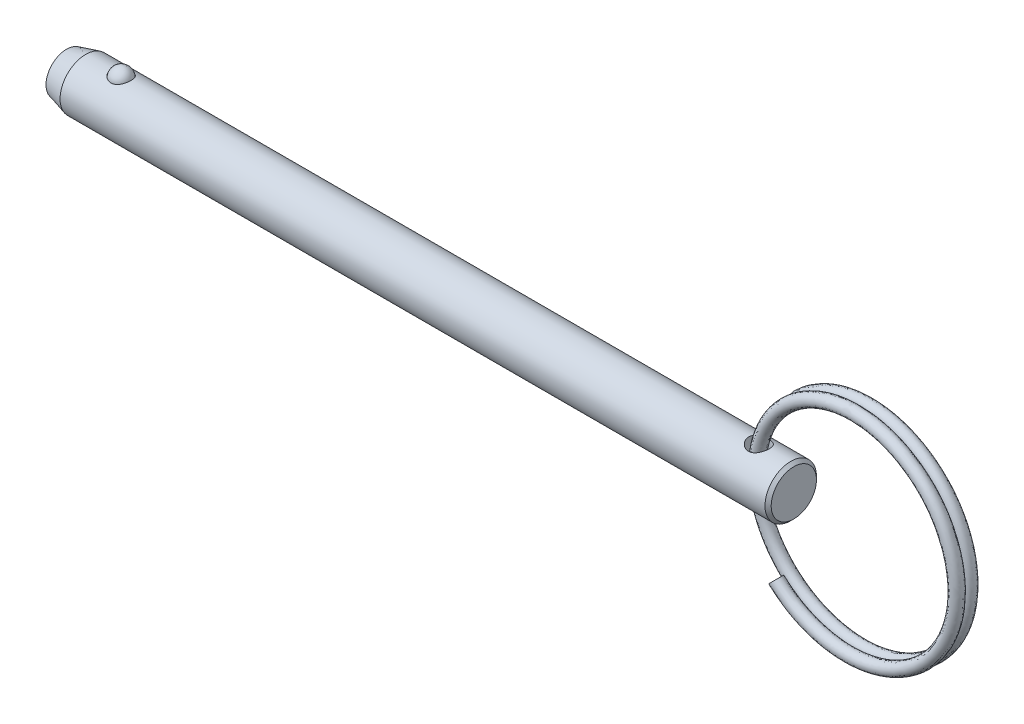
SolidWorks part; units mm, degrees
material "AISI 304"
ref_plane "Front" through (0, 0, 0) normal (0, 0, 1) x (1, 0, 0)
ref_plane "Top" through (0, 0, 0) normal (0, 1, 0) x (1, 0, 0)
ref_plane "Right" through (0, 0, 0) normal (1, 0, 0) x (0, 0, -1)
sketch "Sketch1" plane through (0, 0, 0) normal (0, 0, 1) x (1, 0, 0)
  line L0 (5.588, 2.794) -> (5.207, 3.175)
  line L1 (5.207, 3.175) -> (5.588, 3.175) construction
  line L4 (5.588, 2.794) -> (5.588, 0)
  line L5 (5.588, 3.175) -> (5.588, 2.794) construction
  line L16 (5.207, 3.175) -> (-81.7549, 3.175)
  line L17 (-84.1248, 3.175) -> (-84.1248, 2.54) construction
  line L19 (-81.7549, 3.175) -> (-84.1248, 3.175) construction
  line L22 (-84.1248, -3.175) -> (-81.7549, -3.175) construction
  line L23 (-77.3903, 2.8575) -> (-77.3903, -2.8575) construction
  line L24 (-84.1248, 0) -> (5.588, 0)
  line L27 (5.588, 0) -> (8.382, 0) construction
  line L29 (-84.1248, 0) -> (-84.1248, -2.54) construction
  line L36 (0, 0) -> (0, 3.175) construction
  line L37 (-84.1248, 2.54) -> (-84.1248, 0)
  line L38 (-81.7549, -3.175) -> (5.588, -3.175) construction
  line L39 (-84.1248, -2.54) -> (-84.1248, -3.175) construction
  line L40 (-81.7549, 3.175) -> (-84.1248, 2.54)
  line L42 (-81.7549, -3.175) -> (-84.1248, -2.54) construction
  line L43 (-81.7549, 3.175) -> (-81.7549, -3.175) construction
  circle A2 centre (-77.3903, 2.8575) radius 1.2319 construction
  point P35 (-76.2, 3.175)
  dimension "D2" = 5.715
  dimension "D11" = 0.9144
  dimension "A" = 6.35
  dimension "D" = 5.588
  dimension "E" = 7.2644
  dimension "D3" = 0.381
  dimension "Useable Length" = 76.2
  dimension "D12" = 5.08
  dimension "C" = 7.9248
  dimension "A1" = 15
revolve "Revolve1" add sketch "Sketch1" angle 360 about L27
sketch "Sketch2" plane through (0, 0, 0) normal (0, 0, 1) x (1, 0, 0)
  line L0 (-76.133, 2.8575) -> (-78.6476, 2.8575)
  line L1 (-77.3903, 4.0894) -> (-77.3903, 4.1148) construction
  line L2 (-76.133, 2.8575) -> (-73.6184, 2.8575) construction
  circle A0 centre (-77.3903, 2.8575) radius 1.2319 construction
  circle A1 centre (-77.3903, 2.8575) radius 1.2319 construction
  arc A2 (-78.6476, 2.8575) -> (-76.133, 2.8575) centre (-77.3903, 2.8575) cw
  dimension "D1" = 0.0254
revolve "Cut-Revolve1" cut sketch "Sketch2" angle 360 about L2
sketch "Sketch3" plane through (0, 0, 0) normal (0, 0, 1) x (1, 0, 0)
  line L0 (-76.1584, 2.8575) -> (-78.6222, 2.8575)
  line L1 (-76.1584, 2.8575) -> (-73.6946, 2.8575) construction
  circle A0 centre (-77.3903, 2.8575) radius 1.2319 construction
  arc A1 (-76.1584, 2.8575) -> (-78.6222, 2.8575) centre (-77.3903, 2.8575) ccw
revolve "Revolve2" add sketch "Sketch3" angle 360 about L1
sketch "Sketch4" plane through (0, 0, 0) normal (0, 0, 1) x (1, 0, 0)
  line L1 (1.27, -3.175) -> (2.54, -3.175)
  line L2 (1.27, -3.175) -> (1.27, 3.175)
  line L3 (1.27, 3.175) -> (2.54, 3.175)
  line L4 (2.54, -3.175) -> (2.54, 3.175)
  line L5 (1.27, -3.175) -> (1.27, -4.445) construction
  line L6 (2.54, 3.175) -> (5.588, 3.175) construction
  line L8 (0, -3.175) -> (0, 3.175) construction
  line L9 (0, 0) -> (1.27, 0) construction
  line L11 (1.27, 0) -> (2.54, 0) construction
  line L12 (5.207, 3.175) -> (-81.7549, 3.175) construction
  line L14 (-81.7549, -3.175) -> (5.588, -3.175) construction
  dimension "D1" = 2.54
revolve "Cut-Revolve2" cut sketch "Sketch4" angle 360 about L2
sketch "Sketch5" plane through (0, 0, 0) normal (0, 0, 1) x (1, 0, 0)
  line L0 (0, 0) -> (0.293, 0) construction
  line L1 (0.293, 0) -> (0.293, 3.175) construction
  line L2 (5.207, 3.175) -> (-81.7549, 3.175) construction
  line L3 (13.755, 0) -> (27.217, 0) construction
  line L4 (2.54, 3.175) -> (2.247, 3.175) construction
  line L5 (1.27, 3.175) -> (2.54, 3.175) construction
  line L6 (0.6728, 3.175) -> (0.6728, -3.175) construction
  line L7 (0.293, 3.175) -> (0, 3.175) construction
  line L8 (1.27, -3.175) -> (2.54, -3.175) construction
  line L9 (0.6728, -3.175) -> (2.54, -3.175) construction
  line L10 (0.293, 0) -> (13.755, 0) construction
  line L11 (13.755, 0) -> (8.7098, -10.8195) construction
  line L12 (2.247, 3.175) -> (0.6728, 3.175) construction
  line L13 (13.755, 11.938) -> (13.755, 13.462) construction
  line L14 (8.7098, -10.8195) -> (8.3878, -11.5101) construction
  circle A0 centre (13.755, 0) radius 13.462
  circle A1 centre (13.755, 0) radius 11.938 construction
  circle A2 centre (13.755, 0) radius 12.7 construction
  point P26 (13.755, 12.7)
  dimension "D1" = 65
  dimension "R Ring Dia" = 25.4
  dimension "Ring OD" = 1.524
curve "Helix/Spiral1" pitch 1.5494 height 1.3557 radius 13.462 left hand yes centre (13.755, 0, 0) axis (0, 0, -1) start towards (1, 0, 0)
sketch "Sketch6" plane through (114.0038, 0, 0) normal (0, 1, 0) x (0, 0, -1)
  line L0 (0, 112.1868) -> (0, 112.9488) construction
  line L1 (0, 112.9488) -> (0, 113.7108) construction
  circle A0 centre (0, 112.9488) radius 0.762
  dimension "D1" = 1.524
sketch "Sketch7" plane through (0, 0, 0) normal (0, 0, 1) x (1, 0, 0)
  circle A0 centre (13.755, 0) radius 13.462 construction
  circle A1 centre (13.755, 0) radius 13.462
curve "Helix/Spiral2" pitch 1.5494 height 1.3557 radius 13.462 left hand yes centre (13.755, 0, 0) axis (0, 0, 1) start towards (1, 0, 0)
sweep "Sweep1" add profiles "Sketch6" path "Helix/Spiral1"
sweep "Sweep2" add profiles "Sketch6<2>" path "Helix/Spiral2"
sketch "Sketch6<2>" plane through (114.0038, 0, 0) normal (0, 1, 0) x (0, 0, -1) same geometry as "Sketch6"
ref_plane "Plane1" through (0, -10.8195, 0) normal (0, 1, 0) x (-1, 0, 0)
sketch "Sketch8" plane through (0, -10.8195, 0) normal (0, 1, 0) x (-1, 0, 0)
  line L0 (296.0902, 0) -> (-8.7098, 0) construction
  line L1 (10.3402, -0.7779) -> (4.5066, -0.7779)
  line L2 (3.5004, -0.9415) -> (-7.2005, -4.517)
  line L3 (-7.2005, 4.517) -> (3.5004, 0.9415)
  line L4 (4.5066, 0.7779) -> (282.8738, 0.7779)
  line L5 (283.88, 0.9415) -> (294.5809, 4.517)
  line L6 (277.0402, -0.7779) -> (282.8738, -0.7779)
  line L7 (283.88, -0.9415) -> (294.5809, -4.517)
  line L8 (10.3402, -0.7779) -> (10.3402, 0.7779) construction
  arc A0 (-7.2005, 4.517) -> (-7.2005, -4.517) centre (-8.7098, 0) ccw
  arc A1 (294.5809, -4.517) -> (294.5809, 4.517) centre (296.0902, 0) ccw
  arc A2 (4.5066, -0.7779) -> (3.5004, -0.9415) centre (4.5066, -3.9529) ccw
  arc A3 (3.5004, 0.9415) -> (4.5066, 0.7779) centre (4.5066, 3.9529) ccw
  arc A4 (282.8738, -0.7779) -> (283.88, -0.9415) centre (282.8738, -3.9529) cw
  arc A5 (282.8738, 0.7779) -> (283.88, 0.9415) centre (282.8738, 3.9529) ccw
  point P6 (10.3402, 0)
  point P16 (3.9902, -0.7779)
  point P20 (3.9902, 0.7779)
  point P23 (283.3902, -0.7779)
  point P26 (283.3902, 0.7779)
  dimension "D2" = 4.7625
  dimension "D3" = 1.5557
  dimension "D6" = 3.175
  dimension "Lanyard Length" = 304.8
  dimension "D4" = 6.35
  dimension "D5" = 12.7
ref_plane "Plane2" through (-10.3402, 0, 0) normal (1, 0, 0) x (0, 0, -1)
sketch "Sketch9" plane through (-10.3402, 0, 0) normal (1, 0, 0) x (0, 0, -1)
  circle A0 centre (0.7779, -10.8195) radius 0.7779
sweep "Sweep3" [suppressed] add profiles "Sketch9" path "Sketch8"
sketch "Sketch10" [suppressed] plane through (-10.3402, 0, 0) normal (1, 0, 0) x (0, 0, -1)
  arc A0 (-0.3849, -10.1482) -> (-0.3849, -11.4908) centre (-0.7779, -10.8195) ccw
  circle A1 centre (0.7779, -10.8195) radius 0.7779
  arc A2 (0.3849, -11.4908) -> (0.3849, -10.1482) centre (0.7779, -10.8195) ccw
  arc A3 (-0.3849, -11.4908) -> (0.3849, -11.4908) centre (0, -12.1485) cw
  arc A4 (-0.3869, -9.3301) -> (-0.3869, -12.3089) centre (-0.7779, -10.8195) ccw
  arc A5 (0.3869, -12.3089) -> (0.3869, -9.3301) centre (0.7779, -10.8195) ccw
  circle A6 centre (-0.7779, -10.8195) radius 1.5399 construction
  circle A7 centre (-0.7779, -10.8195) radius 0.7779 construction
  arc A8 (-0.3849, -10.1482) -> (0.3849, -10.1482) centre (0, -9.4905) ccw
  arc A9 (-0.3869, -9.3301) -> (0.3869, -9.3301) centre (0, -7.856) ccw
  arc A10 (0.3869, -12.3089) -> (-0.3869, -12.3089) centre (0, -13.783) ccw
  point P4 (-0.034, -10.2746)
  point P8 (2.3178, -10.502)
  point P9 (0.762, -10.502)
  dimension "D3" = 1.524
  dimension "D4" = 0.762
  dimension "D2" = 0.762
  dimension "D1" = 0
extrude "Extrude1" [suppressed] add sketch "Sketch10" along normal blind 5.715 separate body
sketch "Sketch11" [suppressed] plane through (-277.0402, 0, 0) normal (1, 0, 0) x (0, 0, -1)
  arc A4 (-0.3849, -10.1482) -> (-0.3849, -11.4908) centre (-0.7779, -10.8195) ccw
  arc A5 (0.3849, -11.4908) -> (-0.3849, -11.4908) centre (0, -12.1485) ccw
  arc A6 (0.3849, -11.4908) -> (0.3849, -10.1482) centre (0.7779, -10.8195) ccw
  arc A7 (-0.3849, -10.1482) -> (0.3849, -10.1482) centre (0, -9.4905) ccw
  arc A8 (-0.3849, -10.1482) -> (-0.3849, -11.4908) centre (-0.7779, -10.8195) ccw
  arc A9 (0.3849, -11.4908) -> (-0.3849, -11.4908) centre (0, -12.1485) ccw
  arc A10 (0.3849, -11.4908) -> (0.3849, -10.1482) centre (0.7779, -10.8195) ccw
  arc A11 (-0.3849, -10.1482) -> (0.3849, -10.1482) centre (0, -9.4905) ccw
  arc A12 (-0.3869, -9.3301) -> (-0.3869, -12.3089) centre (-0.7779, -10.8195) ccw
  arc A13 (0.3869, -12.3089) -> (-0.3869, -12.3089) centre (0, -13.783) ccw
  arc A14 (0.3869, -12.3089) -> (0.3869, -9.3301) centre (0.7779, -10.8195) ccw
  arc A15 (-0.3869, -9.3301) -> (0.3869, -9.3301) centre (0, -7.856) ccw
  arc A16 (-0.3869, -9.3301) -> (-0.3869, -12.3089) centre (-0.7779, -10.8195) ccw
  arc A17 (0.3869, -12.3089) -> (-0.3869, -12.3089) centre (0, -13.783) ccw
  arc A18 (0.3869, -12.3089) -> (0.3869, -9.3301) centre (0.7779, -10.8195) ccw
  arc A19 (-0.3869, -9.3301) -> (0.3869, -9.3301) centre (0, -7.856) ccw
  dimension "D1" = 0
  dimension "D2" = 0
extrude "Extrude2" [suppressed] add sketch "Sketch11" against normal blind 5.715 separate body
sketch "Sketch12" plane through (0, -10.8195, 0) normal (0, 1, 0) x (-1, 0, 0)
  line L0 (326.8712, -5.2864) -> (321.3086, -5.2864) construction
  line L1 (326.8712, -5.9214) -> (310.5026, -5.9214)
  line L2 (326.8712, -5.9214) -> (326.8712, -4.6514)
  line L3 (326.8712, -4.6514) -> (310.7265, -4.6514)
  line L4 (310.5026, -5.9214) -> (310.7265, -4.6514) construction
  line L5 (310.5026, -5.9214) -> (295.1212, -0.3231)
  line L6 (321.3086, -5.2864) -> (310.6146, -5.2864) construction
  line L7 (310.7265, -4.6514) -> (295.5555, 0.8704)
  line L8 (295.1212, -0.3231) -> (295.5555, 0.8704)
  line L9 (310.6146, -5.2864) -> (300.5655, -1.6289) construction
  line L10 (300.5655, -1.6289) -> (295.3383, 0.2737) construction
  arc A0 (294.5809, -4.517) -> (294.5809, 4.517) centre (296.0902, 0) ccw construction
  dimension "D1" = 20
  dimension "D2" = 31.75
  dimension "D3" = 1.27
  dimension "D4" = 5.5626
extrude "Extrude3" [suppressed] add sketch "Sketch12" along normal mid plane 12.7 separate body
sketch "Sketch13" [suppressed] plane through (0, 0, -4.6514) normal (0, 0, 1) x (1, 0, 0)
  line L0 (-326.8712, -10.8195) -> (-310.7265, -10.8195) construction
  line L1 (-324.8782, -4.4695) -> (-326.8712, -4.4695)
  line L2 (-326.8712, -4.4695) -> (-310.7265, -4.4695) construction
  line L3 (-326.8712, -4.4695) -> (-328.8642, -4.4695)
  line L4 (-328.8642, -4.4695) -> (-328.8642, -17.1695)
  line L5 (-328.8642, -17.1695) -> (-326.8712, -17.1695)
  line L6 (-326.8712, -17.1695) -> (-324.8782, -17.1695)
  line L7 (-326.8712, -17.1695) -> (-310.7265, -17.1695) construction
  arc A0 (-324.8782, -4.4695) -> (-324.8782, -17.1695) centre (-315.7587, -10.8195) ccw
  circle A1 centre (-321.3086, -10.8195) radius 2.5781
  dimension "D1" = 5.1562
  dimension "D2" = 11.1125
extrude "Extrude4" [suppressed] cut sketch "Sketch13" against normal up to surface (1.27 mm away)
sketch "Sketch14" [suppressed] plane through (-34.8532, 0, 95.7583) normal (-0.342, 0, 0.9397) x (0.9397, 0, 0.342)
  line L3 (-279.4267, -4.4695) -> (-277.4337, -4.4695)
  line L4 (-277.4337, -4.4695) -> (-275.4407, -4.4695)
  line L5 (-275.4407, -4.4695) -> (-275.4407, -17.1695)
  line L6 (-275.4407, -17.1695) -> (-277.4337, -17.1695)
  line L7 (-277.4337, -17.1695) -> (-279.4267, -17.1695)
  line L8 (-277.4337, -4.4695) -> (-277.4337, -17.1695) construction
  line L9 (-293.5783, -4.4695) -> (-277.4337, -4.4695) construction
  line L10 (-293.6903, -10.8195) -> (-282.9963, -10.8195) construction
  arc A0 (-279.4267, -17.1695) -> (-279.4267, -4.4695) centre (-288.5462, -10.8195) ccw
  circle A1 centre (-282.9963, -10.8195) radius 2.5781
  dimension "D1" = 5.1562
  dimension "D2" = 11.1125
extrude "Extrude6" [suppressed] cut sketch "Sketch14" against normal up to surface (1.27 mm away)
sketch "Sketch15" [suppressed] plane through (0, 0, 0) normal (0, 0, 1) x (1, 0, 0)
  line L1 (-257.8086, -4.4695) -> (-99.0586, -4.4695)
  line L2 (-257.8086, -4.4695) -> (-270.5086, -17.1695)
  line L3 (-270.5086, -17.1695) -> (-111.7586, -17.1695)
  line L4 (-99.0586, -4.4695) -> (-111.7586, -17.1695)
  line L5 (-324.8782, -4.4695) -> (-310.7265, -4.4695) construction
  line L6 (-324.8782, -17.1695) -> (-310.7265, -17.1695) construction
  circle A0 centre (-321.3086, -10.8195) radius 2.5781 construction
  dimension "D1" = 63.5
  dimension "D2" = 158.75
  dimension "D3" = 45
extrude "Extrude7" [suppressed] cut sketch "Sketch15" against normal through all and the other way through all
move or copy body "Body-Move/Copy1" [suppressed] bodies to move or copy 147 151 144 copy no translate (152.4, 0, 0)
sketch "Sketch16" [suppressed] plane through (0, 0, 0) normal (0, 0, 1) x (1, 0, 0)
  line L0 (-111.7586, -6.057) -> (-111.7586, -9.232) construction
  line L1 (-111.7586, -9.232) -> (-109.2186, -8.2795) construction
  line L2 (-109.2186, -8.2795) -> (-114.2986, -13.3595) construction
  line L3 (-114.2986, -13.3595) -> (-111.7586, -12.407) construction
  line L4 (-111.7586, -12.407) -> (-111.7586, -15.582) construction
  line L5 (-112.5364, -11.5974) -> (-110.9807, -10.0416) construction
  line L6 (-105.4086, -15.582) -> (-105.4086, -12.407) construction
  line L7 (-105.4086, -12.407) -> (-107.9486, -13.3595) construction
  line L8 (-107.9486, -13.3595) -> (-102.8686, -8.2795) construction
  line L9 (-102.8686, -8.2795) -> (-105.4086, -9.232) construction
  line L10 (-105.4086, -9.232) -> (-105.4086, -6.057) construction
  line L11 (-104.6307, -10.0416) -> (-106.1864, -11.5974) construction
  line L14 (-4.5066, -10.8195) -> (-282.8738, -10.8195) construction
  dimension "D1" = 3.175
  dimension "D2" = 3.175
  dimension "D3" = 5.08
  dimension "D4" = 1.5875
equation "\"D12@Sketch1\"=\"A@Sketch1\" * 0.80"
equation "\"D2@Sketch1\"=\"A@Sketch1\" * 0.9"
equation "\"D1@Sketch4\" = \"A@Sketch1\" / 2.5"
equation "\"Ring OD@Sketch5\" = \"R Ring Dia@Sketch5\" * 0.06"
equation "\"D4@Helix/Spiral1\"=\"Ring OD@Sketch5\" + 0.001"
equation "\"D1@Sketch6\"=\"Ring OD@Sketch5\""
equation "\"D4@Helix/Spiral2\" = \"D4@Helix/Spiral1\""
equation "\"D5@Helix/Spiral2\" = \"D5@Helix/Spiral1\""
equation "\"D1@Sketch14\" = \"D1@Sketch13\""
equation "\"D2@Sketch14\" = \"D2@Sketch13\""
